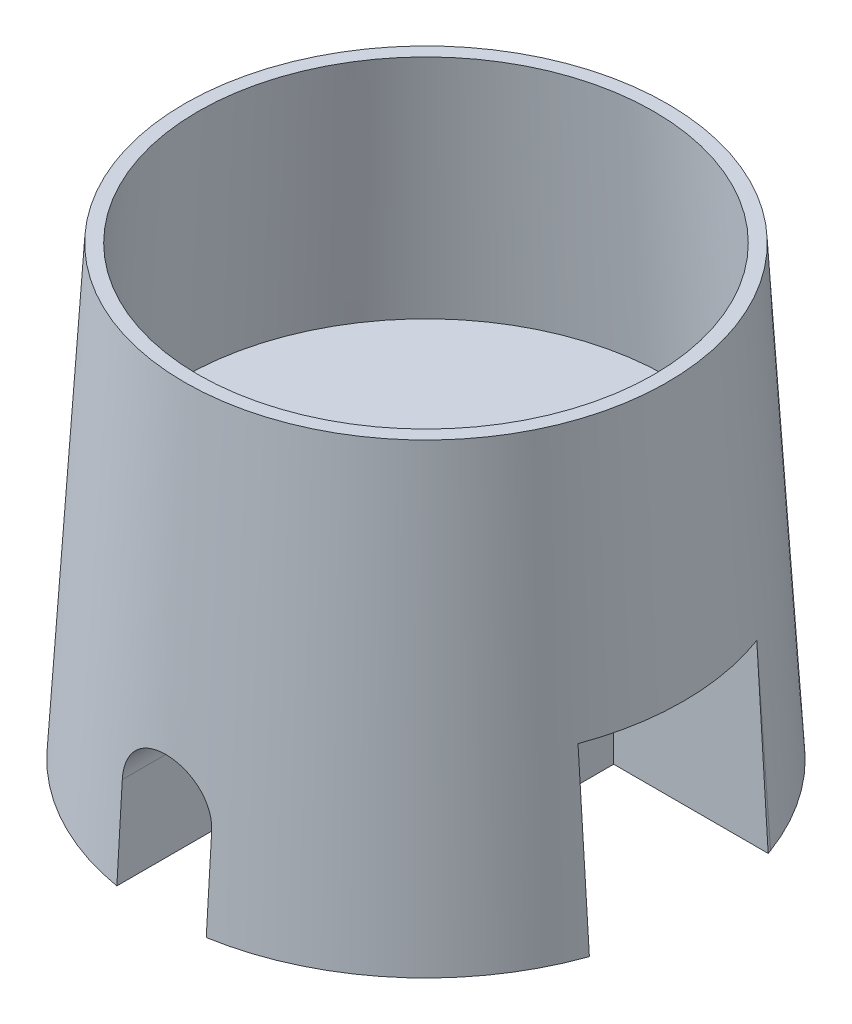
SolidWorks part; units mm, degrees
ref_plane "前视基准面" through (0, 0, 0) normal (0, 0, 1) x (1, 0, 0)
ref_plane "上视基准面" through (0, 0, 0) normal (0, 1, 0) x (1, 0, 0)
ref_plane "右视基准面" through (0, 0, 0) normal (1, 0, 0) x (0, 0, -1)
sketch "草图3" plane through (0, 0, 0) normal (1, 0, 0) x (0, 0, -1)
  line L0 (0, 0) -> (60, 0)
  line L1 (60, 0) -> (54, 100)
  line L2 (54, 100) -> (0, 100)
  line L3 (0, 100) -> (0, 0)
  dimension "D1" = 100
  dimension "D2" = 54
  dimension "D3" = 60
revolve "旋转2" add sketch "草图3" angle 360 about L3
sketch "草图5" plane through (0, 0, 0) normal (0, -1, 0) x (-1, 0, 0)
  line L0 (0, 0) -> (0, 71.9204) construction
  line L1 (0, 0) -> (72.7838, 0) construction
  line L3 (20, -30) -> (-20, -30)
  line L4 (20, -30) -> (20, 30)
  line L5 (20, 30) -> (-20, 30)
  line L6 (-20, -30) -> (-20, 30)
  dimension "D1" = 60
  dimension "D2" = 40
extrude "切除-拉伸1" cut sketch "草图5" against normal blind 40
sketch "草图6" plane through (0, 0, 0) normal (1, 0, 0) x (0, 0, -1)
  line L0 (0, 0) -> (0, 62.3248) construction
  line L1 (-60, 0) -> (60, 0) construction
  line L2 (-20, 0) -> (20, 0)
  line L3 (-20, 0) -> (-20, 40)
  line L4 (-20, 40) -> (20, 40)
  line L5 (20, 0) -> (20, 40)
  dimension "D1" = 40
  dimension "D2" = 40
extrude "切除-拉伸2" cut sketch "草图6" against normal blind 40 from offset 22 offset against normal yes
sketch "草图9" plane through (0, 0, 0) normal (1, 0, 0) x (0, 0, -1)
  line L0 (0, 0) -> (0, 62.3248) construction
  line L2 (-20, 0) -> (20, 0)
  line L3 (-20, 0) -> (-20, 40)
  line L4 (-20, 40) -> (20, 40)
  line L5 (20, 0) -> (20, 40)
  dimension "D1" = 40
  dimension "D2" = 40
extrude "切除-拉伸3" cut sketch "草图9" along normal blind 40 from offset 22
sketch "草图10" plane through (0, 0, 30) normal (0, 0, -1) x (-1, 0, 0)
  line L0 (0, 0) -> (0, 41.5034) construction
  line L1 (-10, 0) -> (-10, 20)
  line L2 (-56.5685, 0) -> (56.5685, 0) construction
  line L3 (-10, 0) -> (10, 0)
  line L4 (10, 0) -> (10, 20)
  arc A0 (-10, 20) -> (10, 20) centre (0, 20) cw
  dimension "D3" = 10
  dimension "D1" = 10
  dimension "D2" = 20
extrude "切除-拉伸4" cut sketch "草图10" against normal blind 40
sketch "草图11" plane through (0, 0, 0) normal (0, 0, 1) x (1, 0, 0)
  line L0 (-50.9946, 100) -> (-54.1746, 47)
  line L1 (54, 100) -> (-54, 100) construction
  line L2 (-54.1746, 47) -> (0, 47)
  line L3 (0, 47) -> (0, 100)
  line L4 (0, 100) -> (-50.9946, 100)
  line L5 (-54, 100) -> (-57.6, 40) construction
  dimension "D1" = 53
  dimension "D2" = 3
revolve "切除-旋转1" cut sketch "草图11" angle 360 about L3
hole_wizard "Ø2.5mm 暗销孔1" positions "草图14" profile "草图15" hole size "Ø2.5" standard "ISO" end condition through all
sketch "草图14" plane through (0, 47, 0) normal (0, 1, 0) x (1, 0, 0)
  line L0 (0, 0) -> (97.1322, 0) construction
  line L2 (0, 0) -> (0, -66.7943) construction
  point P17 (-10.5, 13.5)
  point P21 (-10.5, -13.5)
  point P22 (41.5, 13.5)
  point P29 (36.705, 11.4489)
  point P30 (0, 0)
  point P31 (0, 0)
  point P32 (41.5, -13.5)
  dimension "D1" = 13.5
  dimension "D2" = 10.5
  dimension "D3" = 52
  dimension "D4" = 13.5
sketch "草图15" plane through (41.5, 47, 13.5) normal (1, 0, 0) x (0, 0, 1)
  line L0 (0, 0) -> (0, 47)
  line L1 (0, 47) -> (1.25, 47)
  line L2 (1.25, 47) -> (1.25, 0.025)
  line L3 (1.25, 0.025) -> (1.275, 0)
  line L5 (1.275, 0) -> (0, 0)
  line L6 (-1.25, 0.025) -> (-1.275, 0) construction
  line L11 (0, -6.35) -> (0, 107.95) construction
  dimension "通孔孔直径" = 2.5
  dimension "通孔孔深度" = 47
  dimension "近端锥形沉头孔直径" = 2.55
  dimension "近端锥形沉头孔角度" = 90
